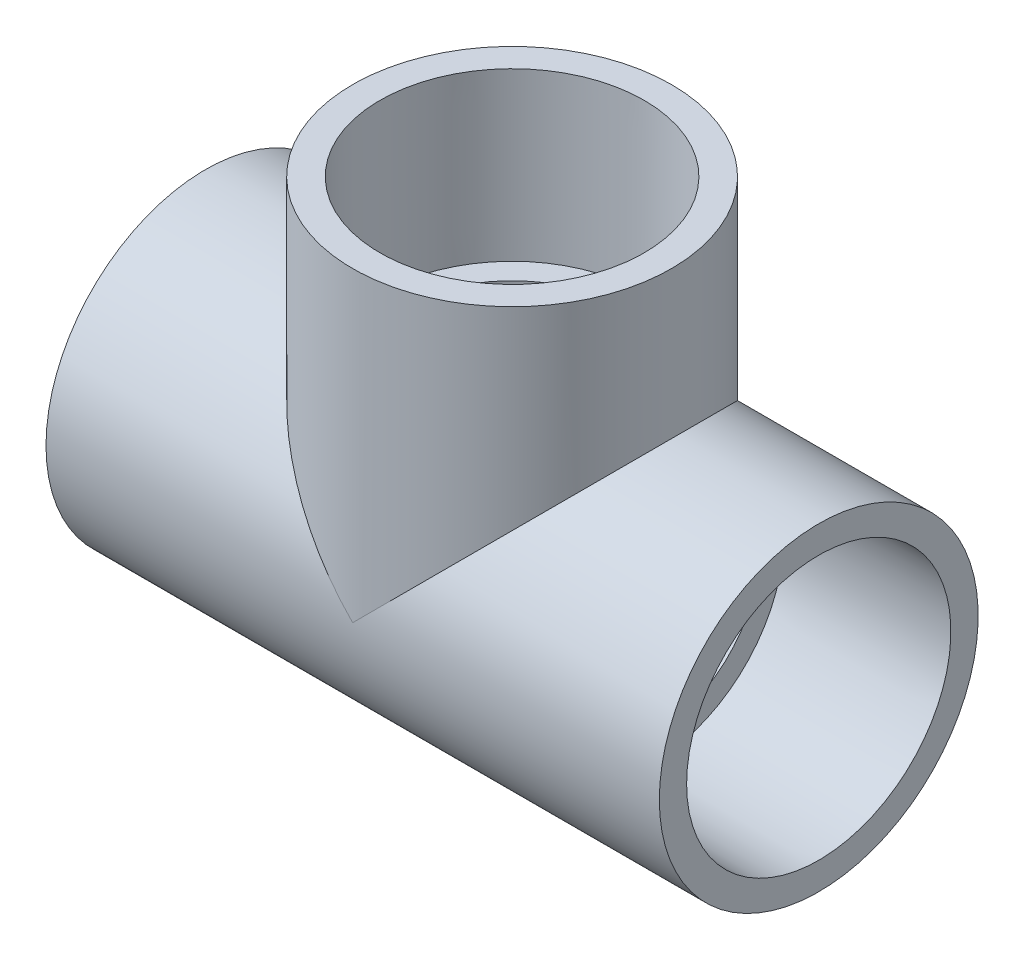
SolidWorks part; units mm, degrees
ref_plane "Front Plane" through (0, 0, 0) normal (0, 0, 1) x (1, 0, 0)
ref_plane "Top Plane" through (0, 0, 0) normal (0, 1, 0) x (1, 0, 0)
ref_plane "Right Plane" through (0, 0, 0) normal (1, 0, 0) x (0, 0, -1)
sketch "Sketch0" plane through (0, 0, 0) normal (0, 0, 1) x (1, 0, 0)
  line L0 (-70.358, 0) -> (0, 0) construction
  line L1 (0, 0) -> (0, 70.358) construction
  line L2 (-32.258, 0) -> (0, 0) construction
  line L3 (0, 0) -> (0, 32.258) construction
  line L4 (-70.358, 36.576) -> (-70.358, -36.576) construction
  line L5 (-32.258, 30.0863) -> (-70.358, 30.3149) construction
  line L6 (-32.258, 30.0863) -> (-32.258, -30.0863) construction
  line L7 (-32.258, -30.0863) -> (-70.358, -30.3149) construction
  line L8 (-70.358, 30.3149) -> (-70.358, -30.3149) construction
  line L9 (-36.576, 70.358) -> (36.576, 70.358) construction
  line L10 (-30.3149, 70.358) -> (30.3149, 70.358) construction
  line L11 (30.3149, 70.358) -> (30.0863, 32.258) construction
  line L12 (30.0863, 32.258) -> (-30.0863, 32.258) construction
  line L13 (-30.0863, 32.258) -> (-30.3149, 70.358) construction
  line L14 (-32.258, 24.6253) -> (-32.258, -24.6253) construction
  line L18 (-24.6253, 32.258) -> (24.6253, 32.258) construction
  dimension "H" = 70.358
  dimension "G" = 32.258
  dimension "M" = 73.152
  dimension "OD A" = 60.6298
  dimension "OD B" = 60.1726
  dimension "ID" = 49.2506
sketch "Sketch1" plane through (0, 0, 0) normal (0, 0, 1) x (1, 0, 0)
  line L0 (-70.358, 0) -> (0, 0) construction
  line L1 (-70.358, 0) -> (0, 0) construction
  line L3 (-70.358, -36.576) -> (-32.258, -36.576)
  line L4 (-70.358, -36.576) -> (-70.358, -30.3149)
  line L5 (-70.358, -30.3149) -> (-32.258, -30.0863)
  line L6 (-32.258, -36.576) -> (-32.258, -30.0863)
revolve "Revolve1" add sketch "Sketch1" angle 360 about L1
mirror "Mirror1" about plane through (0, 0, 0) normal (1, 0, 0) of bodies 102
sketch "Sketch2" plane through (0, 0, 0) normal (0, 0, 1) x (1, 0, 0)
  line L0 (30.3149, 70.358) -> (30.0863, 32.258)
  line L1 (30.0863, 32.258) -> (36.576, 32.258)
  line L2 (36.576, 32.258) -> (36.576, 70.358)
  line L3 (36.576, 70.358) -> (30.3149, 70.358)
  line L4 (0, 0) -> (0, 70.358) construction
  line L5 (0, 0) -> (0, 70.358) construction
revolve "Revolve2" add sketch "Sketch2" angle 360 about L5
sketch "Sketch3" plane through (-32.258, 0, 0) normal (1, 0, 0) x (0, 0, -1)
  line L0 (-36.576, 32.258) -> (36.576, 32.258) construction
  line L2 (17.2402, 32.258) -> (-17.2402, 32.258)
  circle A1 centre (0, 0) radius 36.576 construction
  arc A3 (-17.2402, 32.258) -> (17.2402, 32.258) centre (0, 0) ccw
extrude "Boss-Extrude1" add sketch "Sketch3" along normal up to surface (64.516 mm away) up to face at (32.258, 0, 30.0863)
sketch "Sketch4" plane through (0, 32.258, 0) normal (0, -1, 0) x (1, 0, 0)
  line L0 (32.258, -17.2402) -> (32.258, 17.2402)
  line L1 (-32.258, -17.2402) -> (-32.258, 17.2402)
  circle A0 centre (0, 0) radius 36.576 construction
  arc A1 (32.258, 17.2402) -> (-32.258, 17.2402) centre (0, 0) ccw
  arc A2 (-32.258, -17.2402) -> (32.258, -17.2402) centre (0, 0) ccw
  circle A3 centre (0, 0) radius 36.576 construction
  circle A4 centre (0, 0) radius 36.576 construction
extrude "Boss-Extrude2" add sketch "Sketch4" along normal up to surface (32.258 mm away) up to plane "Top Plane"
sketch "Sketch5" plane through (-32.258, 0, 0) normal (-1, 0, 0) x (0, 0, 1)
  line L0 (0, 30.0863) -> (0, -30.0863) construction
  circle A0 centre (0, 0) radius 24.6253
extrude "Cut-Extrude1" cut sketch "Sketch5" against normal up to surface (64.516 mm away) up to face at (32.258, 0, 30.0863)
sketch "Sketch6" plane through (0, 32.258, 0) normal (0, 1, 0) x (1, 0, 0)
  circle A0 centre (0, 0) radius 24.6253
extrude "Cut-Extrude2" cut sketch "Sketch6" against normal up to vertex (32.258 mm away) up to point (0, 0, 0)
ref_axis "Center Axis 1" through (70.358, 0, 0) along (-1, 0, 0)
ref_axis "Center Axis 2" through (0, 70.358, 0) along (0, -1, 0)
